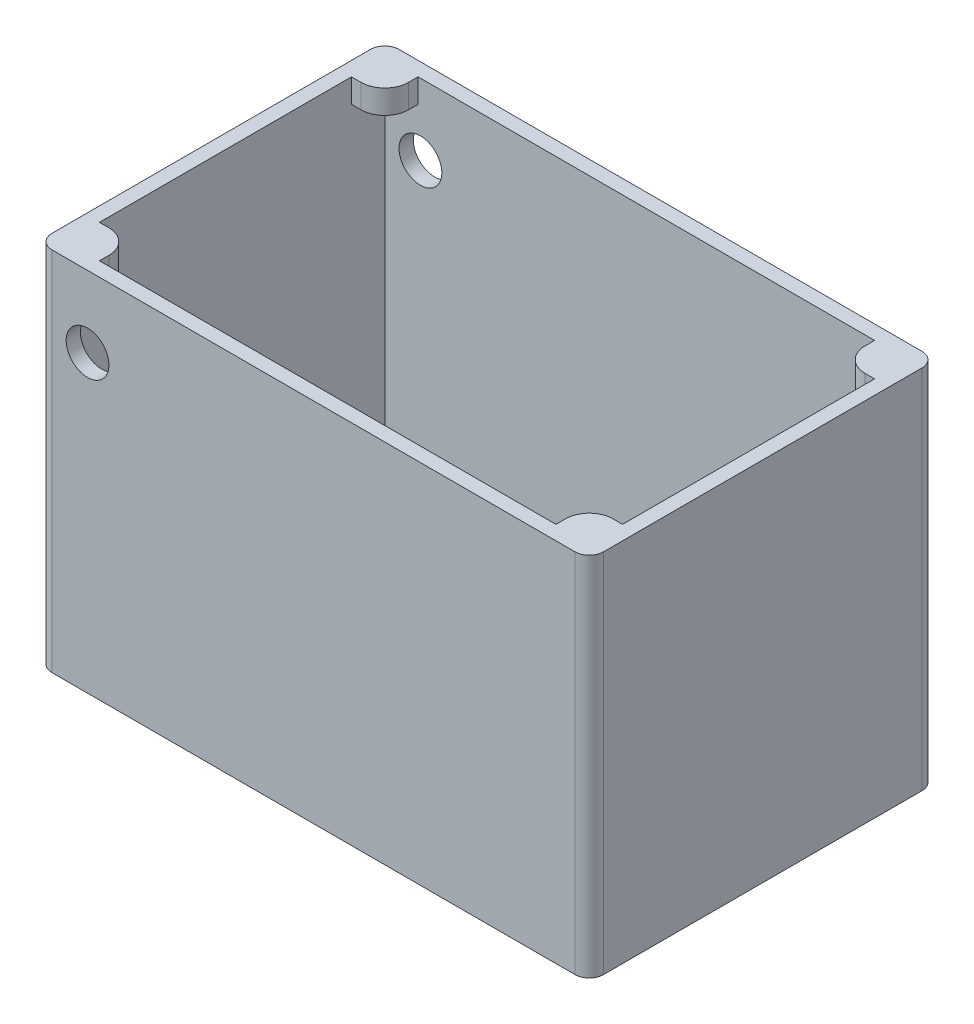
SolidWorks part; units mm, degrees
ref_plane "Front" through (0, 0, 0) normal (0, 0, 1) x (1, 0, 0)
ref_plane "Top" through (0, 0, 0) normal (0, 1, 0) x (1, 0, 0)
ref_plane "Right" through (0, 0, 0) normal (1, 0, 0) x (0, 0, -1)
sketch "Sketch1" plane through (0, 0, 0) normal (0, 1, 0) x (1, 0, 0)
  line L1 (-58, -36.5) -> (58, -36.5)
  line L2 (-58, -36.5) -> (-58, 36.5)
  line L3 (-58, 36.5) -> (58, 36.5)
  line L4 (58, -36.5) -> (58, 36.5)
  line L5 (-58, -36.5) -> (58, 36.5) construction
  line L6 (-58, 36.5) -> (58, -36.5) construction
  point P0 (0, 0)
extrude "Boss-Extrude1" add sketch "Sketch1" along normal blind 77
sketch "Sketch2" plane through (0, 77, 0) normal (0, 1, 0) x (1, 0, 0)
  line L0 (-55, 33.5) -> (-55, 36.5) construction
  line L1 (-55, -33.5) -> (55, -33.5)
  line L2 (-55, -33.5) -> (-55, 33.5)
  line L3 (-55, 33.5) -> (55, 33.5)
  line L4 (55, -33.5) -> (55, 33.5)
  line L5 (-55, -33.5) -> (55, 33.5) construction
  line L6 (-55, 33.5) -> (55, -33.5) construction
  line L7 (58, 36.5) -> (-58, 36.5) construction
  line L8 (-55, 36.5) -> (-58, 36.5) construction
  point P0 (0, 0)
  dimension "D1" = 3
  dimension "D2" = 3
extrude "Cut-Extrude3" cut sketch "Sketch2" against normal blind 73.5
sketch "Sketch11" plane through (0, 0, 33.5) normal (0, 0, -1) x (-1, 0, 0)
  circle A0 centre (47.5, 62) radius 4.5
  point P0 (0, 0)
extrude "Cut-Extrude6" cut sketch "Sketch11" against normal through all both and the other way through all
sketch "Sketch12" plane through (0, 77, 0) normal (0, 1, 0) x (1, 0, 0)
  line L1 (58, 36.5) -> (48, 36.5)
  line L2 (58, 36.5) -> (58, 26.5)
  line L3 (58, 26.5) -> (48, 26.5)
  line L4 (48, 36.5) -> (48, 26.5)
  line L5 (58, -36.5) -> (48, -36.5)
  line L6 (58, -36.5) -> (58, -26.5)
  line L7 (58, -26.5) -> (48, -26.5)
  line L8 (48, -36.5) -> (48, -26.5)
  line L9 (-58, 36.5) -> (-48, 36.5)
  line L10 (-58, 36.5) -> (-58, 26.5)
  line L11 (-58, 26.5) -> (-48, 26.5)
  line L12 (-48, 36.5) -> (-48, 26.5)
  line L13 (-58, -36.5) -> (-48, -36.5)
  line L14 (-58, -36.5) -> (-58, -26.5)
  line L15 (-58, -26.5) -> (-48, -26.5)
  line L16 (-48, -36.5) -> (-48, -26.5)
extrude "Boss-Extrude5" add sketch "Sketch12" against normal blind 5
fillet "Fillet1" radius 3 1 edges at (-58, 38.5, -36.5) type face fillet first side face at (0, 38.5, -36.5) second side face at (-58, 38.5, 0)
fillet "Fillet2" radius 3 1 edges at (-58, 38.5, 36.5) type face fillet first side face at (0, 38.5, 36.5) second side face at (-58, 38.5, 1.5)
fillet "Fillet3" radius 3 1 edges at (58, 38.5, 36.5) type face fillet first side face at (58, 38.5, 0) second side face at (1.5, 38.5, 36.5)
fillet "Fillet4" radius 3 1 edges at (58, 38.5, -36.5) type face fillet first side face at (58, 38.5, -1.5) second side face at (1.5, 38.5, -36.5)
fillet "Fillet5" radius 5 1 edges at (-48, 74.5, -26.5) type face fillet first side face at (-51.5, 74.5, -26.5) second side face at (-48, 74.5, -30)
fillet "Fillet6" radius 5 1 edges at (-48, 74.5, 26.5) type face fillet first side face at (-51.5, 74.5, 26.5) second side face at (-48, 74.5, 30)
fillet "Fillet7" radius 5 1 edges at (48, 74.5, -26.5) type face fillet first side face at (51.5, 74.5, -26.5) second side face at (48, 74.5, -30)
fillet "Fillet8" radius 5 1 edges at (48, 74.5, 26.5) type face fillet first side face at (51.5, 74.5, 26.5) second side face at (48, 74.5, 30)
